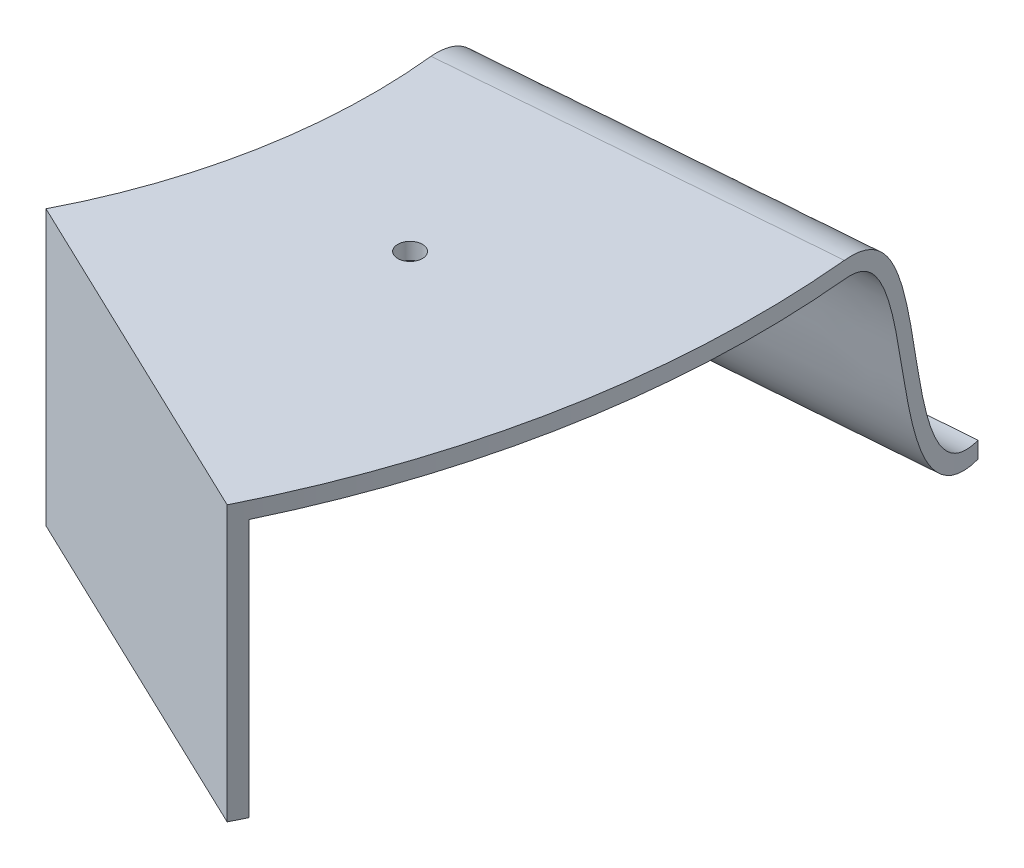
SolidWorks part; units mm, degrees
ref_plane "Front Plane" through (0, 0, 0) normal (0, 0, 1) x (1, 0, 0)
ref_plane "Top Plane" through (0, 0, 0) normal (0, 1, 0) x (1, 0, 0)
ref_plane "Right Plane" through (0, 0, 0) normal (1, 0, 0) x (0, 0, -1)
ref_plane "Plane4" through (0, -10, 0) normal (0, 1, 0) x (1, 0, 0)
sketch "Sketch2" plane through (0, 0, 0) normal (0, 1, 0) x (1, 0, 0)
  circle A1 centre (0, 0) radius 178
  circle A2 centre (0, 0) radius 100
extrude "Boss-Extrude1" add sketch "Sketch2" along normal blind 3
sketch "Sketch3" plane through (0, 3, 0) normal (0, 1, 0) x (1, 0, 0)
  circle A0 centre (0, 0) radius 175
  circle A1 centre (0, 0) radius 178
  dimension "D1" = 3
extrude "Boss-Extrude2" add sketch "Sketch3" along normal blind 60
sketch "Sketch5" plane through (0, 3, 0) normal (0, 1, 0) x (1, 0, 0)
  line L0 (0, 0) -> (174.4708, 13.5988)
  line L1 (0, 0) -> (157.8956, -75.4585)
  line L2 (174.4708, 13.5988) -> (45.5792, 75.1963)
  circle A1 centre (0, 0) radius 175 construction
  arc A2 (99.6976, 7.7707) -> (90.226, -43.1191) centre (0, 0) cw
  circle A3 centre (0, 0) radius 100 construction
  arc A4 (174.4708, 13.5988) -> (157.8956, -75.4585) centre (0, 0) cw
  circle M3 centre (0, 0) radius 100
  circle M4 centre (0, 0) radius 175
  dimension "D1" = 30
  dimension "D2" = 30
extrude "Cut-Extrude2" cut sketch "Sketch5" against normal blind 25 contours L1 L0 M3 M4
ref_plane "Plane2" [suppressed] through (0, 30, 0) normal (0, 1, 0) x (1, 0, 0)
sketch "Sketch8" plane through (0, -10, 0) normal (0, 1, 0) x (1, 0, 0)
  line L1 (97.4441, -46.5687) -> (157.8956, -75.4585)
  line L2 (174.6783, 10.6059) -> (174.704, 10.6079)
  line L3 (159.1659, -72.7406) -> (159.1892, -72.7517)
  line L4 (98.7001, -43.8439) -> (159.1892, -72.7517) construction
  line L5 (107.865, 5.3982) -> (174.704, 10.6079) construction
  line L6 (104.6825, 8.1593) -> (174.4708, 13.5988) construction
  line L7 (94.7373, -45.2751) -> (157.8956, -75.4585) construction
  line L8 (93.4051, -47.9634) -> (156.602, -78.1653)
  line L9 (104.4066, 11.1469) -> (107.3988, 11.3801)
  line L10 (107.6734, 8.3924) -> (174.4708, 13.5988) construction
  line L11 (174.2121, 16.5877) -> (174.2377, 16.5897)
  line L12 (104.4066, 11.1469) -> (174.2377, 16.5897) construction
  arc A0 (156.5788, -78.1542) -> (157.8956, -75.4585) centre (0, 0) ccw
  arc A2 (97.4441, -46.5687) -> (107.6734, 8.3924) centre (0, 0) ccw
  arc A3 (93.4051, -47.9634) -> (104.4066, 11.1469) centre (0, 0) ccw
  arc A4 (97.4441, -46.5687) -> (107.3988, 11.3801) centre (0, 0) ccw
  arc A5 (98.7001, -43.8439) -> (107.865, 5.3982) centre (0, 0) ccw
  arc A6 (94.7373, -45.2751) -> (104.6825, 8.1593) centre (0, 0) ccw construction
  arc A7 (174.6783, 10.6059) -> (174.2121, 16.5877) centre (0, 0) ccw
  dimension "D1" = 3
  dimension "D2" = 3
extrude "Boss-Extrude4" add sketch "Sketch8" against normal blind 50 contours A2 A4 L9 A3 L8 A0 L1
sketch "Sketch9" plane through (0, -10, 0) normal (0, -1, 0) x (-1, 0, 0)
  line L0 (-104.4066, 11.1469) -> (-107.3988, 11.3801) construction
  line L1 (-104.4066, 11.1469) -> (-174.2121, 16.5877)
  line L2 (-93.4051, -47.9634) -> (-156.5788, -78.1542) construction
  line L3 (-93.4051, -47.9634) -> (-156.5788, -78.1542)
  arc A2 (-174.2121, 16.5877) -> (-156.5788, -78.1542) centre (0, 0) ccw
  arc A4 (-104.4066, 11.1469) -> (-93.4051, -47.9634) centre (0, 0) ccw
  arc A5 (-104.4066, 11.1469) -> (-93.4051, -47.9634) centre (0, 0) ccw construction
  arc A6 (-157.8956, -75.4585) -> (-156.5788, -78.1542) centre (0, 0) ccw construction
extrude "Boss-Extrude5" add sketch "Sketch9" along normal blind 3
ref_plane "Plane3" through (104.6398, 0, -8.1559) normal (0.997, 0, -0.0777) x (0, 1, 0)
sketch "Sketch14" plane through (104.6398, 0, -8.1559) normal (0.997, 0, -0.0777) x (0, 1, 0)
  line L0 (-10, -3) -> (-10, 55.0766) construction
  line L1 (-56, -33.1496) -> (-10, -3) construction
  line L2 (-56, -33.1496) -> (-59, -33.1496)
  line L3 (-13, -3) -> (-10, -3)
  spline S0 degree 3 poles (-10, -3) (-10, -24.1671) (-56, -11.9826) (-56, -33.1496) knots 0 0 0 0 1 1 1 1
  spline S1 degree 1 poles (-13, -3) (-59, -33.1496) knots 0 0 1 1 construction
  spline S2 degree 3 poles (-13, -3) (-13, -3.2527) (-13.0178, -3.7721) (-13.1185, -4.6961) (-13.3548, -5.7283) (-13.7907, -6.7963) (-14.5724, -8.0736) (-15.969, -9.5012) (-18.418, -11.0219) (-21.5602, -12.3095) (-26.4646, -13.7386) (-33.5237, -15.1217) (-42.302, -16.8338) (-49.0623, -19.0089) (-53.703, -21.8305) (-56.6113, -24.7325) (-58.2374, -27.9057) (-58.8096, -30.4435) (-58.9729, -31.9628) (-59, -32.7566) (-59, -33.1496) knots 0 0 0 0 0.015625 0.03125 0.0625 0.09375 0.125 0.1875 0.25 0.3125 0.375 0.5 0.625 0.75 0.8125 0.875 0.9375 0.96875 0.984375 1 1 1 1
  dimension "D1" = 4
  dimension "D2" = 55
  dimension "D3" = 3
extrude "Boss-Extrude15" add sketch "Sketch14" along normal up to surface (70.0171 mm away)
sketch "Sketch15" plane through (-0.2331, 0, -2.9909) normal (-0.0777, 0, -0.997) x (-0.997, 0, 0.0777)
  line L0 (-107.9583, -60) -> (-107.9583, -13) construction
  line L1 (-104.9571, -10) -> (-107.9583, -10)
  line L2 (-104.9571, -10) -> (-104.9571, -59)
  line L3 (-104.9571, -59) -> (-107.9583, -59)
  line L4 (-107.9583, -10) -> (-107.9583, -59)
  line L5 (-104.9571, -60) -> (-107.9583, -60) construction
  dimension "D1" = 1
extrude "Boss-Extrude16" add sketch "Sketch15" along normal up to surface (1.3777 mm away)
fillet "Fillet2" radius 10 1 edges at (105.9027, -59, -11.2635)
sketch "Sketch16" plane through (0, -10, 0) normal (0, 1, 0) x (1, 0, 0)
  circle A0 centre (0, 0) radius 178
extrude "Cut-Extrude3" cut sketch "Sketch16" along normal up to surface (73 mm away) up to face at (0, 63, 178)
sketch "Sketch17" plane through (0, -10, 0) normal (0, 1, 0) x (1, 0, 0)
  line L0 (0, 0) -> (133.2708, -21.5385) construction
  line L1 (133.2708, -21.5385) -> (172.7584, -27.9202) construction
  circle A0 centre (133.2708, -21.5385) radius 2.25
  arc A2 (156.5788, -78.1542) -> (174.2121, 16.5877) centre (0, 0) ccw construction
  dimension "D1" = 4.5
  dimension "D2" = 40
  dimension "D3" = 18
extrude "Cut-Extrude4" cut sketch "Sketch17" against normal up to next
